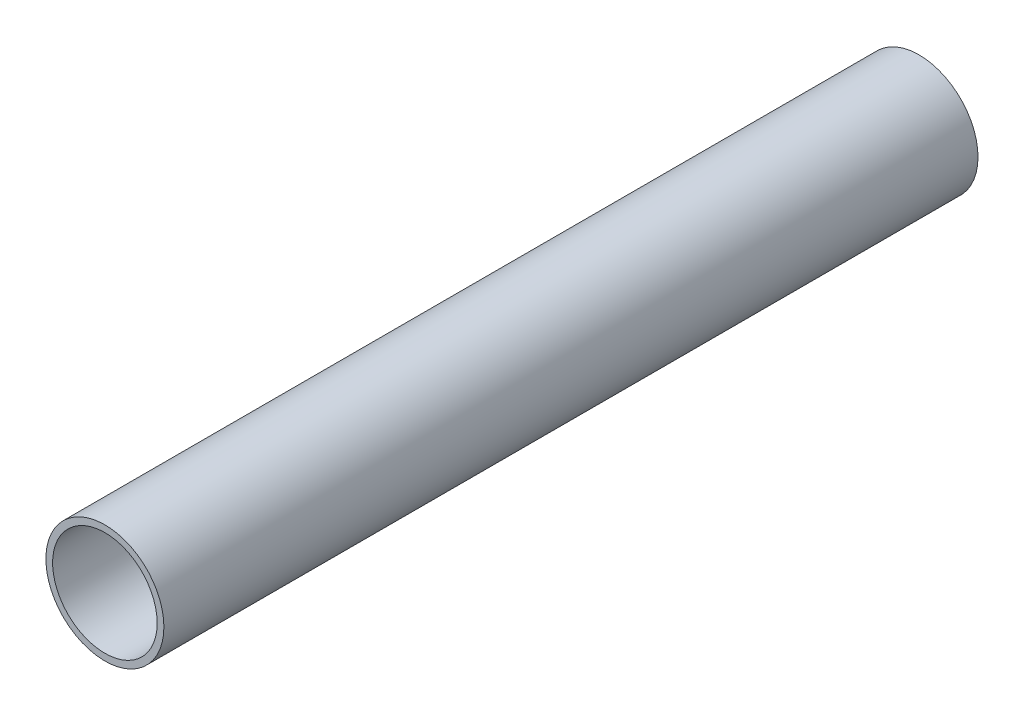
SolidWorks part; units mm, degrees
material "PLA"
ref_plane "Alzado" through (0, 0, 0) normal (0, 0, 1) x (1, 0, 0)
ref_plane "Planta" through (0, 0, 0) normal (0, 1, 0) x (1, 0, 0)
ref_plane "Vista lateral" through (0, 0, 0) normal (1, 0, 0) x (0, 0, -1)
sketch "Croquis1" plane through (0, 0, 0) normal (0, 0, 1) x (1, 0, 0)
  circle A0 centre (0, 0) radius 15.54
  circle A1 centre (0, 0) radius 17.54
  dimension "D1" = 35.08
  dimension "D2" = 31.08
extrude "Saliente-Extruir1" add sketch "Croquis1" along normal blind 242
equation "\"DouterAblative\"=35.08"
equation "\"D1@Croquis1\"=\"DouterAblative\""
equation "\"DinnerAblative\" = \"DouterAblative\" - \"AblativeThickness\" * 2"
equation "\"D2@Croquis1\"=\"DinnerAblative\""
equation "\"LengthAblative\"=242"
equation "\"D1@Saliente-Extruir1\"=\"LengthAblative\""
equation "\"AblativeThickness\"= 2"
